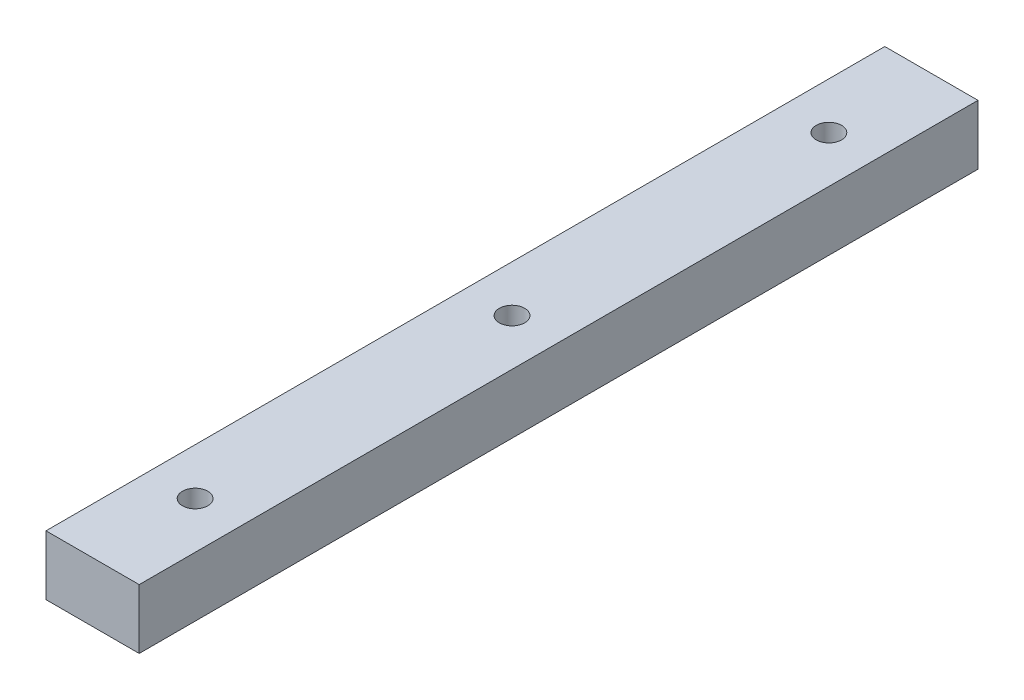
SolidWorks part; units mm, degrees
material "Plain Carbon Steel"
ref_plane "Front Plane" through (0, 0, 0) normal (0, 0, 1) x (1, 0, 0)
ref_plane "Top Plane" through (0, 0, 0) normal (0, 1, 0) x (1, 0, 0)
ref_plane "Right Plane" through (0, 0, 0) normal (1, 0, 0) x (0, 0, -1)
sketch "Sketch1" plane through (0, 0, 0) normal (0, 1, 0) x (1, 0, 0)
  line L1 (-12.5, -112.5) -> (12.5, -112.5)
  line L2 (-12.5, -112.5) -> (-12.5, 112.5)
  line L3 (-12.5, 112.5) -> (12.5, 112.5)
  line L4 (12.5, -112.5) -> (12.5, 112.5)
  line L5 (-12.5, -112.5) -> (12.5, 112.5) construction
  line L6 (-12.5, 112.5) -> (12.5, -112.5) construction
  point P0 (0, 0)
  dimension "D1" = 225
  dimension "D2" = 25
extrude "Boss-Extrude1" add sketch "Sketch1" against normal blind 16
sketch "Sketch2" plane through (0, -16, 0) normal (0, -1, 0) x (1, 0, 0)
  circle A0 centre (0, -100) radius 7.5 construction
  circle A1 centre (0, 100) radius 7.5 construction
  circle A2 centre (0, -100) radius 7.5 construction
  circle A3 centre (0, 100) radius 7.5 construction
  circle A4 centre (0, 100) radius 8.5
  circle A5 centre (0, -100) radius 8.5
  dimension "D1" = 17
extrude "Cut-Extrude1" cut sketch "Sketch2" against normal blind 5
hole_wizard "M8 Tapped Hole1" positions "Sketch7" profile "Sketch6" tap size "M8" standard "ISO" end condition through all
sketch "Sketch7" plane through (0, 0, 0) normal (0, 1, 0) x (1, 0, 0)
  point P0 (0, 85)
  point P2 (0, 0)
  point P4 (0, -85)
  dimension "D1" = 0
  dimension "D2" = 85
  dimension "D3" = 85
sketch "Sketch6" plane through (0, 0, -85) normal (1, 0, 0) x (0, 0, 1)
  line L0 (0, 0) -> (0, 16)
  line L1 (0, 16) -> (3.4, 16)
  line L2 (3.4, 16) -> (3.4, 0)
  line L5 (3.4, 0) -> (0, 0)
  line L11 (0, -6.35) -> (0, 107.95) construction
  dimension "Thru Tap Drill Dia." = 6.8
  dimension "Thru Tap Drill Depth" = 16
cosmetic thread "Hole Thread1"
cosmetic thread "Hole Thread2"
cosmetic thread "Hole Thread3"
